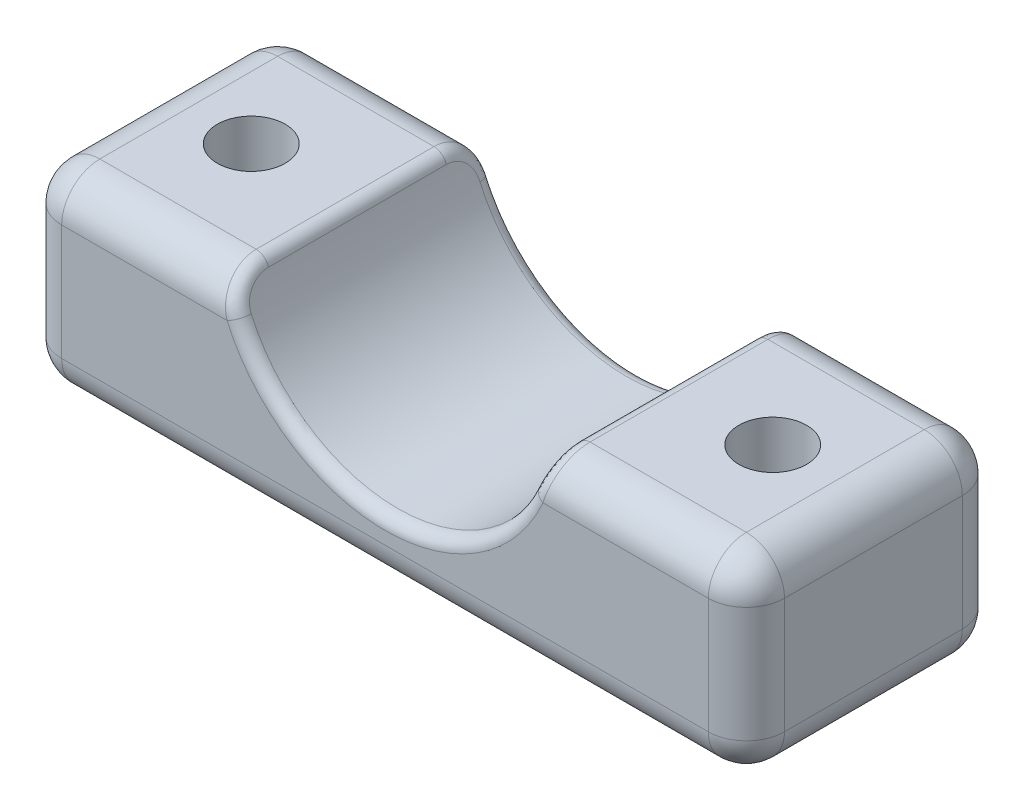
SolidWorks part; units mm, degrees
material "PLA ABS"
ref_plane "Front Plane" through (0, 0, 0) normal (0, 0, 1) x (1, 0, 0)
ref_plane "Top Plane" through (0, 0, 0) normal (0, 1, 0) x (1, 0, 0)
ref_plane "Right Plane" through (0, 0, 0) normal (1, 0, 0) x (0, 0, -1)
sketch "Sketch1" plane through (0, 0, 0) normal (0, 0, 1) x (1, 0, 0)
  line L0 (16.002, 22.352) -> (36.1315, 22.352)
  line L1 (-36.1315, 0) -> (36.1315, 0)
  line L2 (-36.1315, 0) -> (-36.1315, 22.352)
  line L3 (-36.1315, 22.352) -> (-16.002, 22.352)
  line L4 (36.1315, 0) -> (36.1315, 22.352)
  arc A0 (-16.002, 22.352) -> (16.002, 22.352) centre (0, 22.352) ccw
  dimension "D1" = 32.004
  dimension "D2" = 72.263
  dimension "D3" = 6.35
extrude "Boss-Extrude1" add sketch "Sketch1" along normal mid plane 25.4
sketch "Sketch2" plane through (0, 22.352, 0) normal (0, 1, 0) x (1, 0, 0)
  line L0 (-26.0668, 12.7) -> (-26.0667, -12.7) construction
  line L1 (-16.002, 12.7) -> (-36.1315, 12.7) construction
  line L2 (-16.002, -12.7) -> (-36.1315, -12.7) construction
  line L3 (0, 0) -> (0, 12.7) construction
  line L4 (16.002, 12.7) -> (-16.002, 12.7) construction
  circle A0 centre (-26.0668, 0) radius 3.3909
  circle A1 centre (26.0668, 0) radius 3.3909
  dimension "D1" = 6.7818
extrude "Cut-Extrude1" cut sketch "Sketch2" against normal through all
sketch "Sketch3" plane through (0, 0, 12.7) normal (0, 0, 1) x (1, 0, 0)
  line L0 (-16.002, 22.352) -> (-36.1315, 22.352) construction
  line L1 (-36.1315, 26.3528) -> (36.1315, 26.3528)
  line L2 (-36.1315, 26.3528) -> (-36.1315, 19.177)
  line L3 (-36.1315, 19.177) -> (36.1315, 19.177)
  line L4 (36.1315, 26.3528) -> (36.1315, 19.177)
  line L5 (-36.1315, 22.352) -> (-36.1315, 0) construction
  line L6 (36.1315, 0) -> (36.1315, 22.352) construction
  dimension "D1" = 3.175
extrude "Cut-Extrude2" cut sketch "Sketch3" against normal through all
sketch "Sketch6" plane through (0, 0, 0) normal (0, -1, 0) x (1, 0, 0)
  line L1 (-26.0667, -6.5625) -> (-20.3835, -3.2812)
  line L2 (-20.3835, -3.2812) -> (-20.3835, 3.2812)
  line L3 (-20.3835, 3.2812) -> (-26.0668, 6.5625)
  line L4 (-26.0668, 6.5625) -> (-31.75, 3.2812)
  line L5 (-31.75, 3.2812) -> (-31.75, -3.2812)
  line L6 (-31.75, -3.2812) -> (-26.0667, -6.5625)
  line L7 (26.0667, 6.5625) -> (20.3835, 3.2812)
  line L8 (20.3835, 3.2812) -> (20.3835, -3.2812)
  line L9 (20.3835, -3.2812) -> (26.0668, -6.5625)
  line L10 (26.0668, -6.5625) -> (31.75, -3.2812)
  line L11 (31.75, -3.2812) -> (31.75, 3.2812)
  line L12 (31.75, 3.2812) -> (26.0667, 6.5625)
  circle A0 centre (-26.0668, 0) radius 5.6833 construction
  circle A1 centre (26.0668, 0) radius 5.6833 construction
  dimension "D1" = 11.3665
extrude "Cut-Extrude3" cut sketch "Sketch6" against normal blind 4.0716
fillet "Fillet3" radius 3.81 14 edges at (-36.1315, 0, 0) (-36.1315, 9.5885, -12.7) (-36.1315, 19.177, 0) (-36.1315, 9.5885, 12.7) (36.1315, 0, 0) (36.1315, 9.5885, 12.7) (36.1315, 19.177, 0) (36.1315, 9.5885, -12.7) (-25.9077, 19.177, 12.7) (25.9077, 19.177, 12.7) (0, 0, 12.7) (0, 0, -12.7) (25.9077, 19.177, -12.7) (-25.9077, 19.177, -12.7)
fillet "Fillet4" radius 1.27 8 edges at (15.3443, 17.8116, 11.8123) (15.6839, 19.177, 0) (15.5012, 18.3799, -11.2221) (0, 6.35, -12.7) (-15.3443, 17.8116, -11.8123) (-15.6839, 19.177, 0) (-15.5012, 18.3799, 11.2221) (0, 6.35, 12.7)
